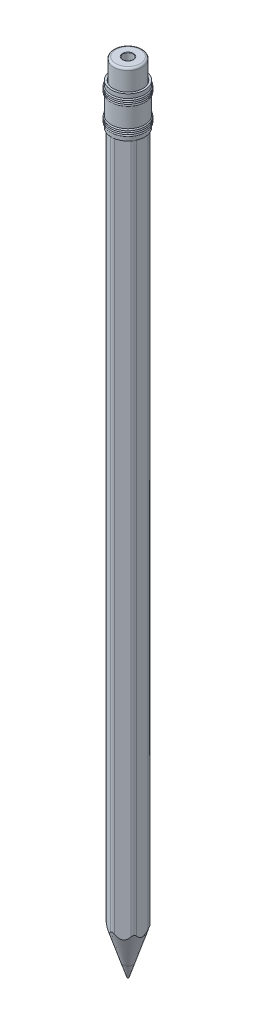
SolidWorks part; units mm, degrees
ref_plane "Front Plane" through (0, 0, 0) normal (0, 0, 1) x (1, 0, 0)
ref_plane "Top Plane" through (0, 0, 0) normal (0, 1, 0) x (1, 0, 0)
ref_plane "Right Plane" through (0, 0, 0) normal (1, 0, 0) x (0, 0, -1)
sketch "Sketch1" plane through (0, 0, 0) normal (0, 1, 0) x (1, 0, 0)
  circle A0 centre (0, 0) radius 1.25
  dimension "D1" = 2.5
extrude "Lead" add sketch "Sketch1" along normal blind 185 contours A0
sketch "Sketch2" plane through (0, 0, 0) normal (0, 1, 0) x (1, 0, 0)
  line L1 (3.5, -2.0207) -> (3.5, 2.0207)
  line L2 (3.5, 2.0207) -> (0, 4.0415)
  line L3 (0, 4.0415) -> (-3.5, 2.0207)
  line L4 (-3.5, 2.0207) -> (-3.5, -2.0207)
  line L5 (-3.5, -2.0207) -> (0, -4.0415)
  line L6 (0, -4.0415) -> (3.5, -2.0207)
  circle A0 centre (0, 0) radius 3.5 construction
  circle A3 centre (0, 0) radius 1.25
  circle A4 centre (0, 0) radius 1.25 construction
  dimension "D1" = 7
extrude "Wooden Casing" add sketch "Sketch2" along normal up to surface (185 mm away) separate body contours L1 L2 L3 L4 L5 L6 up to face at (0, 185, 1.25)
extrude "Cut-Extrude6" cut sketch "Sketch2<4>" along normal up to surface (185 mm away) contours A3 up to face at (0, 185, 0)
sketch "Sketch2<4>" plane through (0, 0, 0) normal (0, 1, 0) x (1, 0, 0) same geometry as "Sketch2"
sketch "Sketch3" plane through (0, 185, 0) normal (0, 1, 0) x (-1, 0, 0)
  circle A0 centre (0, 0) radius 3.5
  dimension "D1" = 7
extrude "Eraser" add sketch "Sketch3" along normal blind 10 separate body
fillet "Fillet1" radius 0.5 1 edges at (0, 195, 3.5)
sketch "Sketch4" plane through (0, 0, 0) normal (0, 0, 1) x (1, 0, 0)
  line L0 (0, 195) -> (0, 0) construction
  line L1 (3, 195) -> (-3, 195) construction
  line L2 (-3.5, 185) -> (1.417, 185) construction
  line L7 (-4.1, 0) -> (0, 0) construction
  line L11 (0, 185) -> (3.5, 185) construction
  line L15 (-4.1, 190) -> (-3.6, 190)
  line L16 (-4.1, 190) -> (-4.1, 180) construction
  line L17 (-4.1, 180) -> (-3.6, 180)
  line L18 (-3.6, 190) -> (-3.6, 180) construction
  line L19 (-3.85, 190) -> (-3.85, 180) construction
  line L20 (-4.1, 189) -> (-4.1, 190)
  line L21 (-3.6, 190) -> (-3.6, 189)
  line L22 (-4.1, 187.4) -> (-4.1, 182.6)
  line L23 (-3.6, 182.6) -> (-3.6, 187.4)
  line L24 (-4.1, 181) -> (-4.1, 180)
  line L25 (-3.6, 181) -> (-3.6, 180)
  arc A18 (-4.1, 181.4) -> (-4.1, 181) centre (-4.1, 181.2) ccw
  arc A19 (-4.1, 181.8) -> (-4.1, 181.4) centre (-4.1, 181.6) ccw
  arc A20 (-4.1, 182.2) -> (-4.1, 181.8) centre (-4.1, 182) ccw
  arc A21 (-4.1, 182.6) -> (-4.1, 182.2) centre (-4.1, 182.4) ccw
  arc A22 (-4.1, 187.4) -> (-4.1, 187.8) centre (-4.1, 187.6) cw
  arc A23 (-4.1, 187.8) -> (-4.1, 188.2) centre (-4.1, 188) cw
  arc A24 (-4.1, 188.2) -> (-4.1, 188.6) centre (-4.1, 188.4) cw
  arc A25 (-4.1, 188.6) -> (-4.1, 189) centre (-4.1, 188.8) cw
  arc A26 (-3.6, 182.6) -> (-3.6, 182.2) centre (-3.6, 182.4) cw
  arc A27 (-3.6, 182.2) -> (-3.6, 181.8) centre (-3.6, 182) cw
  arc A28 (-3.6, 181.8) -> (-3.6, 181.4) centre (-3.6, 181.6) cw
  arc A29 (-3.6, 181.4) -> (-3.6, 181) centre (-3.6, 181.2) cw
  arc A30 (-3.6, 188.6) -> (-3.6, 189) centre (-3.6, 188.8) ccw
  arc A31 (-3.6, 188.2) -> (-3.6, 188.6) centre (-3.6, 188.4) ccw
  arc A32 (-3.6, 187.8) -> (-3.6, 188.2) centre (-3.6, 188) ccw
  arc A33 (-3.6, 187.4) -> (-3.6, 187.8) centre (-3.6, 187.6) ccw
  dimension "D6" = 1.2
  dimension "D5" = 0.4
  dimension "D1" = 10
  dimension "D2" = 0.5
  dimension "D3" = 4.1
  dimension "D4" = 5
revolve "Ferrule" add sketch "Sketch4" angle 360 about L0
fillet "Fillet2" radius 1 6 edges at (3.5, 92.5, 2.0207) (3.5, 92.5, -2.0207) (-3.5, 92.5, -2.0207) (-3.5, 92.5, 2.0207) (0, 92.5, 4.0415) (0, 92.5, -4.0415)
sketch "Sketch5" plane through (-1.75, 0, -3.0311) normal (-0.5, 0, -0.866) x (-0.866, 0, 0.5)
  line L0 (0.9434, 170.7374) -> (0.9434, 143.2432) construction
  line L1 (1.4434, 185) -> (1.4434, 0) construction
  text T0 "Pencil HB" font "Century Gothic" height in points 8
  dimension "D1" = 0.5
extrude "Name_Label" cut sketch "Sketch5" against normal blind 0.1
sketch "Sketch6" plane through (0, 0, 0) normal (0, 0, 1) x (1, 0, 0)
  line L0 (0, 43.7612) -> (0, -20.0068) construction
  line L2 (-5, 15) -> (-0.2, 0)
  line L3 (-0.2, 0) -> (-5, 0)
  line L4 (-5, 0) -> (-5, 15)
  line L7 (-0.5, 0) -> (0.5, 0) construction
  dimension "D1" = 15
  dimension "D2" = 5
  dimension "D3" = 0.2
revolve "Cut-Revolve1" cut sketch "Sketch6" angle 360 about L0
sketch "Sketch7" plane through (0, 195, 0) normal (0, 1, 0) x (1, 0, 0)
  circle A0 centre (0, 0) radius 1.25
  dimension "D1" = 2.5
extrude "Cut-Extrude4" cut sketch "Sketch7" against normal blind 2
fillet "Fillet3" radius 0.1 2 edges at (0, 193, 1.25) (0, 195, 1.25)
